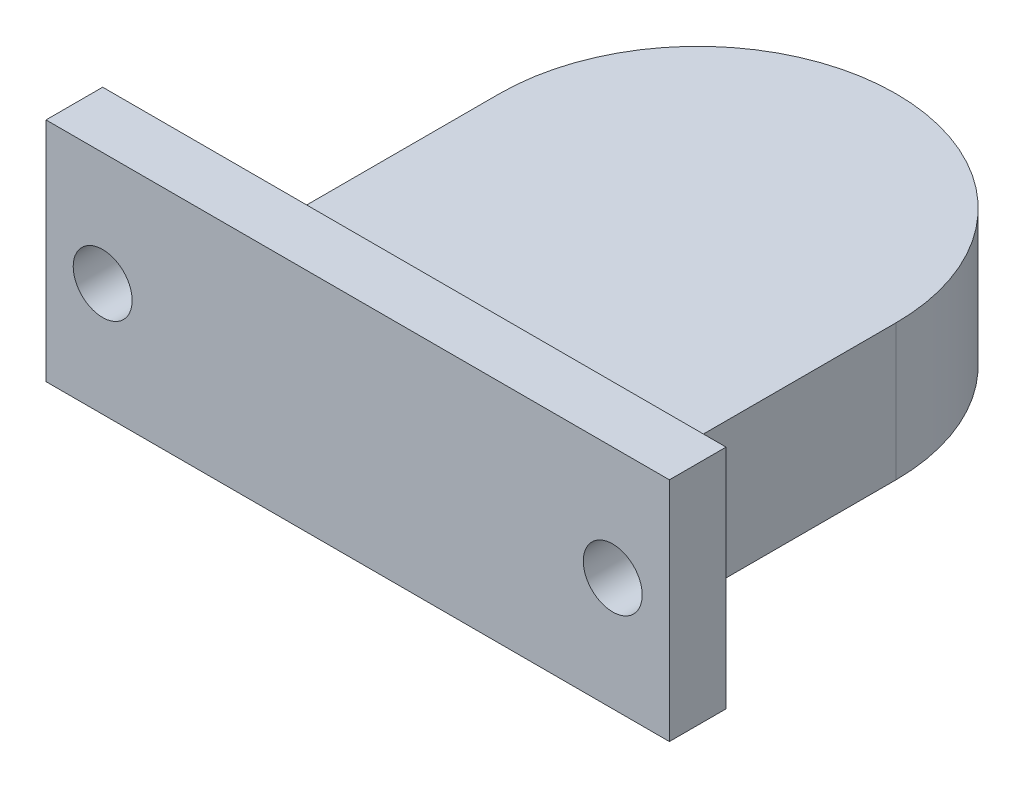
SolidWorks part; units mm, degrees
material "PET"
ref_plane "Front Plane" through (0, 0, 0) normal (0, 0, 1) x (1, 0, 0)
ref_plane "Top Plane" through (0, 0, 0) normal (0, 1, 0) x (1, 0, 0)
ref_plane "Right Plane" through (0, 0, 0) normal (1, 0, 0) x (0, 0, -1)
sketch "Sketch1" plane through (0, 0, 0) normal (0, 1, 0) x (1, 0, 0)
  line L5 (-17.5, 0) -> (-17.5, -25)
  line L6 (17.5, 0) -> (17.5, -25)
  line L9 (-17.5, -25) -> (17.5, -25)
  circle A0 centre (0, 0) radius 11.1
  arc A1 (17.5, 0) -> (-17.5, 0) centre (0, 0) ccw
  dimension "D1" = 22.2
  dimension "D2" = 35
  dimension "D3" = 25
extrude "Boss-Extrude1" add sketch "Sketch1" along normal blind 12
sketch "Sketch3" plane through (0, 12, 0) normal (0, 1, 0) x (1, 0, 0)
  circle A0 centre (0, 0) radius 11.1
  circle A1 centre (0, 0) radius 11.1 construction
extrude "Boss-Extrude2" add sketch "Sketch3" against normal blind 2
sketch "Sketch4" plane through (0, 0, 0) normal (0, 1, 0) x (1, 0, 0)
  line L0 (-17.5, -25) -> (17.5, -25) construction
  line L1 (-27.5, -25) -> (27.5, -25)
  line L2 (-27.5, -25) -> (-27.5, -30)
  line L3 (-27.5, -30) -> (27.5, -30)
  line L4 (27.5, -25) -> (27.5, -30)
  point P6 (0, -25)
  dimension "D1" = 5
  dimension "D2" = 55
extrude "Boss-Extrude3" add sketch "Sketch4" along normal blind 20
sketch "Sketch5" plane through (0, 0, 25) normal (0, 0, -1) x (-1, 0, 0)
  line L0 (-27.5, 10) -> (27.5, 10) construction
  line L1 (-27.5, 20) -> (-27.5, 0) construction
  line L2 (27.5, 20) -> (27.5, 0) construction
  line L3 (-17.5, 12) -> (-17.5, 0) construction
  line L4 (17.5, 12) -> (17.5, 0) construction
  circle A0 centre (22.5, 10) radius 2.6
  circle A1 centre (-22.5, 10) radius 2.6
  dimension "D1" = 5.2
  dimension "D2" = 5.2
  dimension "D3" = 5
  dimension "D4" = 5
  dimension "D5" = 5
  dimension "D6" = 5
extrude "Cut-Extrude1" cut sketch "Sketch5" against normal through all
chamfer "Chamfer1" distance 8 angle 45 1 edges at (0, 12, 25)
equation "\"tolerance\"= 0.2"
equation "\"D1@Sketch1\"=\"tolerance\"+22"
